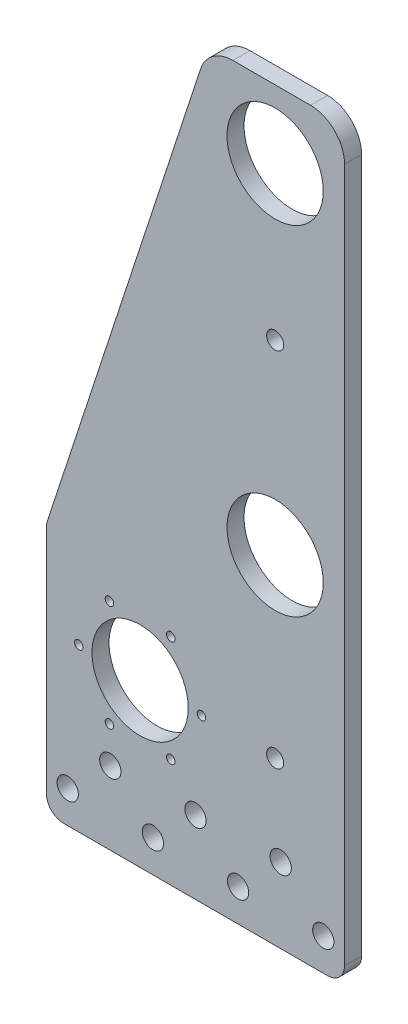
SolidWorks part; units mm, degrees
material "Plain Carbon Steel"
ref_plane "Front Plane" through (0, 0, 0) normal (0, 0, 1) x (1, 0, 0)
ref_plane "Top Plane" through (0, 0, 0) normal (0, 1, 0) x (1, 0, 0)
ref_plane "Right Plane" through (0, 0, 0) normal (1, 0, 0) x (0, 0, -1)
sketch "Sketch1" plane through (0, 0, 0) normal (0, 0, 1) x (1, 0, 0)
  line L2 (88.9, 212.09) -> (88.9, 5.08)
  line L3 (83.82, 0) -> (5.08, 0)
  line L4 (78.74, 222.25) -> (55.6253, 222.25)
  line L5 (45.9692, 215.25) -> (0.252, 75.55)
  line L6 (0, 73.97) -> (0, 5.08)
  line L7 (6.35, 9.652) -> (31.75, 9.652) construction
  line L8 (27.94, 48.354) -> (27.94, 84.1044) construction
  line L9 (27.94, 48.354) -> (60.7143, 48.354) construction
  circle A0 centre (68.199, 201.93) radius 14.351
  circle A1 centre (68.199, 100.838) radius 14.351
  circle A2 centre (68.199, 156.304) radius 2.54
  circle A3 centre (68.199, 48.354) radius 2.54
  arc A4 (78.74, 222.25) -> (88.9, 212.09) centre (78.74, 212.09) cw
  arc A5 (0, 5.08) -> (5.08, 0) centre (5.08, 5.08) ccw
  arc A6 (88.9, 5.08) -> (83.82, 0) centre (83.82, 5.08) cw
  arc A7 (55.6253, 222.25) -> (45.9692, 215.25) centre (55.6253, 212.09) ccw
  arc A8 (0.252, 75.55) -> (0, 73.97) centre (5.08, 73.97) ccw
  circle A9 centre (27.94, 48.354) radius 14.351
  circle A17 centre (68.199, 201.93) radius 50.8 construction
  circle A18 centre (68.199, 100.838) radius 38.1 construction
  circle A19 centre (6.35, 9.652) radius 3.175
  circle A21 centre (31.75, 9.652) radius 3.175
  circle A22 centre (57.15, 9.652) radius 3.175
  circle A23 centre (82.55, 9.652) radius 3.175
  circle A29 centre (69.85, 22.352) radius 3.175
  circle A30 centre (44.45, 21.844) radius 3.175
  circle A31 centre (19.05, 21.844) radius 3.175
  circle A32 centre (46.228, 48.354) radius 1.27
  circle A38 centre (37.084, 32.5161) radius 1.27
  circle A39 centre (18.796, 32.5161) radius 1.27
  circle A40 centre (9.652, 48.354) radius 1.27
  circle A41 centre (18.796, 64.1919) radius 1.27
  circle A42 centre (37.084, 64.1919) radius 1.27
  point P17 (88.9, 222.25)
  point P20 (0, 0)
  point P23 (88.9, 0)
  point P25 (48.26, 222.25)
  point P26 (48.26, 222.25)
  point P40 (0, 0)
  point P43 (27.94, 48.354)
  point P69 (27.94, 48.354)
  dimension "D1" = 28.702
  dimension "D2" = 28.702
  dimension "D4" = 88.9
  dimension "D7" = 5.08
  dimension "D9" = 5.08
  dimension "D11" = 10.16
  dimension "D12" = 5.08
  dimension "D13" = 10.16
  dimension "D14" = 5.08
  dimension "D16" = 28.702
  dimension "D17" = 18.288
  dimension "D23" = 139.7
  dimension "D24" = 101.6
  dimension "D25" = 76.2
  dimension "D26" = 6.35
  dimension "D29" = 21.844
  dimension "D31" = 6.35
  dimension "D32" = 4
  dimension "D34" = 19.05
  dimension "D39" = 21.844
  dimension "D30" = 6.35
  dimension "D35" = 6.35
  dimension "D37" = 6.35
  dimension "D38" = 25.4
  dimension "D18" = 2.54
  dimension "D3" = 101.092
  dimension ".75" = 20.701
  dimension "D5" = 222.25
  dimension "D6" = 20.32
  dimension "D8" = 45.626
  dimension "D10" = 107.95
  dimension "D15" = 40.64
  dimension "D20" = 27.94
  dimension "D21" = 9.144
  dimension "D22" = 15.8379
  dimension "D27" = 9.652
  dimension "D28" = 25.4
  dimension "D33" = 12.7
  dimension "D36" = 25.4
  dimension "D19" = 6
extrude "Boss-Extrude1" add sketch "Sketch1" along normal blind 5.08
